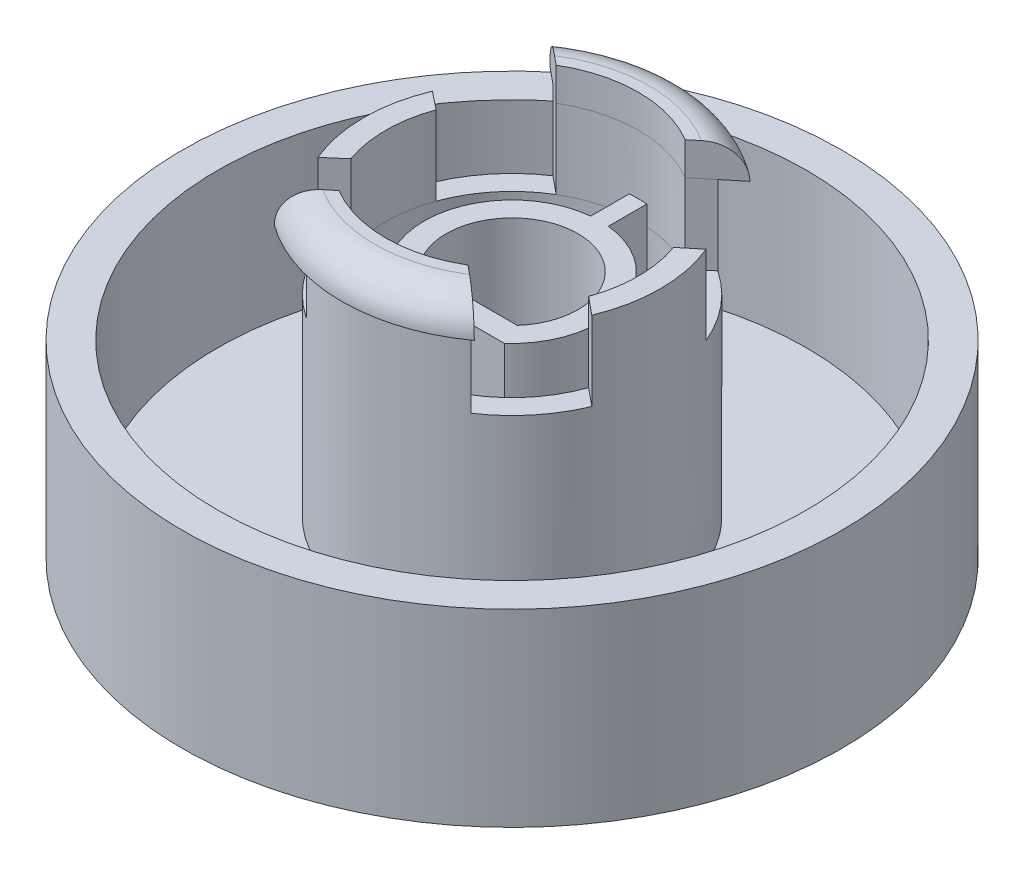
SolidWorks part; units mm, degrees
ref_plane "前视基准面" through (0, 0, 0) normal (0, 0, 1) x (1, 0, 0)
ref_plane "上视基准面" through (0, 0, 0) normal (0, 1, 0) x (1, 0, 0)
ref_plane "右视基准面" through (0, 0, 0) normal (1, 0, 0) x (0, 0, -1)
sketch "草图1" plane through (0, 0, 0) normal (0, 1, 0) x (1, 0, 0)
  circle A0 centre (0, 0) radius 15
extrude "凸台-拉伸1" add sketch "草图1" along normal blind 8.6
shell "抽壳1" thickness 1.6 removed face at (0, 8.6, 15)
sketch "草图2" plane through (0, 1.6, 0) normal (0, 1, 0) x (1, 0, 0)
  circle A0 centre (0, 0) radius 6.75
  circle A1 centre (0, 0) radius 5.75
extrude "凸台-拉伸2" add sketch "草图2" along direction (0, 1, 0) on the side of the normal blind 8.8
sketch "草图5" plane through (0, 10.4, 0) normal (0, 1, 0) x (1, 0, 0)
  line L41 (-6.2292, 2.6) -> (-5.4079, 1.9543)
  line L42 (-3.75, 5.6125) -> (-2.9373, 4.9434)
  line L43 (3.75, 5.6125) -> (2.9373, 4.9434)
  line L44 (6.2292, 2.6) -> (5.4162, 1.9312)
  line L45 (6.2292, -2.6) -> (5.4162, -1.9312)
  line L46 (3.75, -5.6125) -> (2.9373, -4.9434)
  line L47 (-3.75, -5.6125) -> (-2.9373, -4.9434)
  line L48 (-6.2241, -2.6121) -> (-5.4207, -1.9185)
  arc A0 (2.9373, 4.9434) -> (-2.9373, 4.9434) centre (0, 0) ccw
  arc A1 (3.75, 5.6125) -> (-3.75, 5.6125) centre (0, 0) ccw
  arc A2 (-6.2292, 2.6) -> (-6.2241, -2.6121) centre (0, 0) ccw
  arc A3 (-5.4079, 1.9543) -> (-5.4207, -1.9185) centre (0, 0) ccw
  arc A4 (6.2292, -2.6) -> (6.2292, 2.6) centre (0, 0) ccw
  arc A5 (5.4162, -1.9312) -> (5.4162, 1.9312) centre (0, 0) ccw
  arc A6 (-2.9373, -4.9434) -> (2.9373, -4.9434) centre (0, 0) ccw
  arc A7 (-3.75, -5.6125) -> (3.75, -5.6125) centre (0, 0) ccw
extrude "凸台-拉伸4" add sketch "草图5" along normal blind 3.6
sketch "草图14" plane through (0, 14, 0) normal (0, 1, 0) x (1, 0, 0)
  line L0 (-2.9373, 4.9434) -> (-3.75, 5.6125) construction
  line L1 (-3.75, 5.6125) -> (-4.5517, 6.2725) construction
  line L2 (2.9369, 4.9434) -> (3.75, 5.6125) construction
  line L3 (3.75, 5.6125) -> (5.4758, 7.0326) construction
  line L4 (-2.9373, -4.9434) -> (-3.75, -5.6125) construction
  line L5 (-2.9373, -4.9434) -> (-3.75, -5.6125) construction
  line L6 (-2.9375, -4.9436) -> (-3.75, -5.6125) construction
  line L7 (-3.75, -5.6125) -> (-5.4751, -7.0326) construction
  line L8 (-4.5517, 6.2725) -> (-3.75, 5.6125)
  line L9 (2.9369, -4.9434) -> (3.75, -5.6125) construction
  line L10 (3.75, -5.6125) -> (2.9373, -4.9434) construction
  line L11 (-3.75, 5.6125) -> (-2.9371, 4.9433)
  line L13 (2.9369, -4.9434) -> (3.75, -5.6125) construction
  line L14 (3.75, -5.6125) -> (6.3101, -7.7192) construction
  line L15 (4.5519, 6.2724) -> (3.75, 5.6125)
  line L16 (3.75, 5.6125) -> (2.9369, 4.9434)
  line L17 (4.5519, -6.2724) -> (3.75, -5.6125)
  line L18 (3.75, -5.6125) -> (2.9369, -4.9434)
  line L19 (-4.5517, -6.2725) -> (-3.75, -5.6125)
  line L20 (-3.75, -5.6125) -> (-2.9371, -4.9433)
  arc A0 (4.5519, 6.2724) -> (-4.5517, 6.2725) centre (0, 0) ccw
  arc A1 (2.9369, 4.9434) -> (-2.9371, 4.9433) centre (0, 0) ccw
  circle A2 centre (0, 0) radius 6.75 construction
  arc A3 (-2.9371, -4.9433) -> (2.9369, -4.9434) centre (0, 0) ccw
  arc A4 (-4.5517, -6.2725) -> (4.5519, -6.2724) centre (0, 0) ccw
extrude "凸台-拉伸7" add sketch "草图14" along normal blind 1.5
fillet "圆角2" radius 1.5 2 edges at (0.0001, 15.5, 7.75) (0.0001, 15.5, -7.75)
sketch "草图15" plane through (0, 1.6, 0) normal (0, 1, 0) x (1, 0, 0)
  line L0 (0.4, -3) -> (4.9054, -3) construction
  line L1 (8.9231, -3) -> (0.1624, -3) construction
  line L2 (0.1624, -3) -> (0.3108, -5.7416) construction
  line L3 (1.4075, -2) -> (0.4, -2)
  line L4 (1.4075, -2) -> (2.2361, -2)
  line L5 (0.3108, 5.7416) -> (0.4, 7.3887) construction
  line L6 (-0.1622, 2.9956) -> (0, 0) construction
  line L7 (-2.6458, -3) -> (-0.4, -3)
  line L8 (-0.1083, -2) -> (0.1622, 2.9956) construction
  line L10 (-0.4, 5.7361) -> (-0.4, 3.9799)
  line L11 (0.4, -3) -> (2.6458, -3)
  line L12 (0.4, 5.7361) -> (0.4, 3.9799)
  line L13 (-0.4, 7.3887) -> (-0.2162, 3.9942) construction
  line L14 (-0.3108, -5.7416) -> (-0.1622, -2.9956) construction
  line L15 (-0.1624, -3) -> (-10.9906, -3) construction
  line L16 (0.4, -3) -> (0.4, -5.7361)
  line L17 (-0.4, -3) -> (-0.4, -5.7361)
  line L18 (-0.4, -2) -> (-2.2361, -2)
  line L19 (-0.4, -2) -> (0.4, -2)
  arc A0 (2.6458, -3) -> (0.4, 3.9799) centre (0, 0) ccw
  arc A1 (-0.4, 3.9799) -> (-2.6458, -3) centre (0, 0) ccw
  arc A2 (0.4, 5.7361) -> (-0.4, 5.7361) centre (0, 0) ccw
  arc A3 (2.2361, -2) -> (-2.2361, -2) centre (0, 0) ccw
  arc A4 (-0.4, -5.7361) -> (0.4, -5.7361) centre (0, 0) ccw
extrude "凸台-拉伸8" add sketch "草图15" along normal blind 9.7
